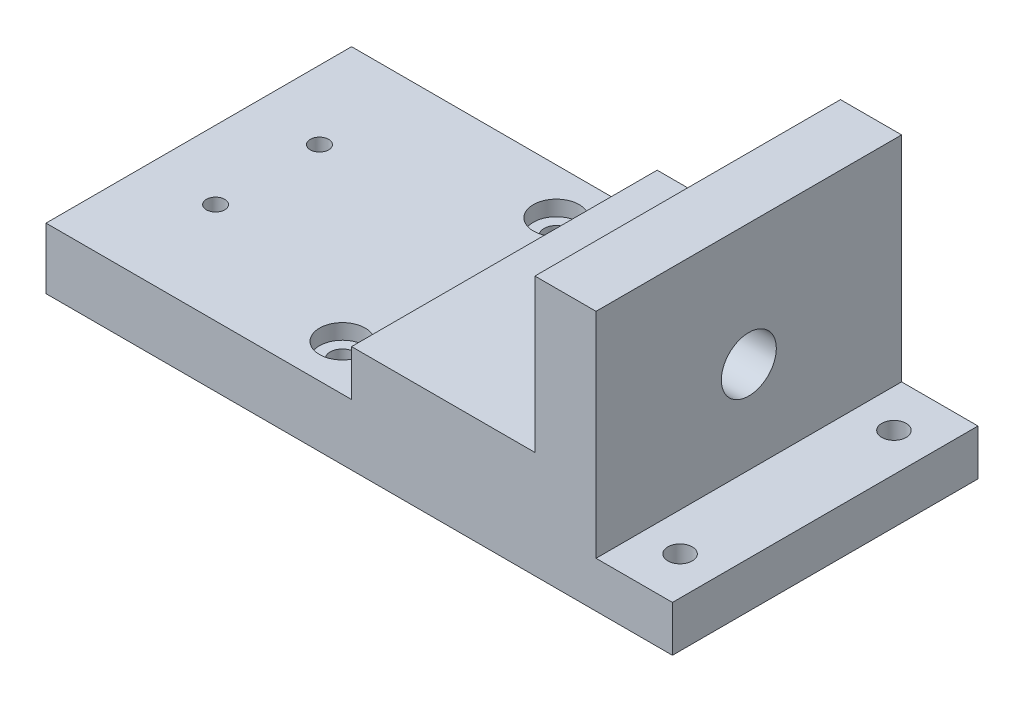
SolidWorks part; units mm, degrees
ref_plane "Front Plane" through (0, 0, 0) normal (0, 0, 1) x (1, 0, 0)
ref_plane "Top Plane" through (0, 0, 0) normal (0, 1, 0) x (1, 0, 0)
ref_plane "Right Plane" through (0, 0, 0) normal (1, 0, 0) x (0, 0, -1)
sketch "Sketch2" plane through (0, 0, 0) normal (0, 0, 1) x (1, 0, 0)
  line L0 (0, 0) -> (0, 15)
  line L1 (0, 15) -> (-25, 15)
  line L2 (-25, 15) -> (-25, 85)
  line L3 (-25, 85) -> (-45, 85)
  line L4 (-45, 85) -> (-45, 35)
  line L5 (-45, 35) -> (-105, 35)
  line L6 (-105, 35) -> (-105, 20)
  line L7 (-105, 20) -> (-205, 20)
  line L8 (-205, 20) -> (-205, 0)
  line L9 (-205, 0) -> (0, 0)
  dimension "D1" = 205
  dimension "D2" = 15
  dimension "D3" = 25
  dimension "D4" = 70
  dimension "D5" = 20
  dimension "D6" = 60
  dimension "D7" = 15
  dimension "D8" = 20
extrude "Boss-Extrude1" add sketch "Sketch2" along normal mid plane 100
sketch "Sketch3" plane through (-25, 0, 0) normal (1, 0, 0) x (0, 0, -1)
  line L0 (-50, 85) -> (50, 85) construction
  circle A0 centre (0, 45) radius 9
  dimension "D1" = 18
  dimension "D2" = 40
extrude "Cut-Extrude1" cut sketch "Sketch3" against normal mid plane 100
sketch "Sketch4" plane through (0, 35, 0) normal (0, 1, 0) x (1, 0, 0)
  line L0 (0, 0) -> (-105, 0) construction
  line L1 (-105, -50) -> (-105, 50) construction
  line L2 (-105, -50) -> (-105, 50) construction
  line L3 (-105, 21) -> (-45, 21)
  line L4 (-105, 21) -> (-105, -21)
  line L5 (-105, -21) -> (-45, -21)
  line L6 (-45, 21) -> (-45, -21)
  line L7 (-45, -50) -> (-45, 50) construction
  dimension "D1" = 42
  dimension "D2" = 21
extrude "Boss-Extrude3" add sketch "Sketch4" against normal up to surface (15 mm away) up to face at (-155, 20, 0)
sketch "Sketch6" plane through (0, 20, 0) normal (0, 1, 0) x (1, 0, 0)
  line L0 (0, 0) -> (-205, 0) construction
  line L1 (-205, -50) -> (-205, 50) construction
  line L2 (0, -50) -> (0, 50) construction
  circle A0 centre (-182.5, 17) radius 3
  circle A1 centre (-123, 35) radius 7.5
  circle A2 centre (-123, 35) radius 4
  circle A3 centre (-12.5, 35) radius 7.5
  circle A4 centre (-12.5, 35) radius 4
  circle A5 centre (-12.5, -35) radius 4
  circle A6 centre (-12.5, -35) radius 7.5
  circle A7 centre (-123, -35) radius 4
  circle A8 centre (-123, -35) radius 7.5
  circle A9 centre (-182.5, -17) radius 3
  dimension "D1" = 6
  dimension "D2" = 17
  dimension "D3" = 22.5
  dimension "D4" = 15
  dimension "D5" = 8
  dimension "D8" = 12.5
  dimension "D6" = 59.5
  dimension "D7" = 35
  dimension "D9" = 35
extrude "Cut-Extrude3" cut sketch "Sketch6" against normal through all contours A4 | A2 | A0 | A5 | A7 | A9
extrude "Cut-Extrude4" cut sketch "Sketch6<4>" against normal blind 5 contours A1 | A3 | A6 | A8
sketch "Sketch6<4>" plane through (0, 20, 0) normal (0, 1, 0) x (1, 0, 0) same geometry as "Sketch6"
